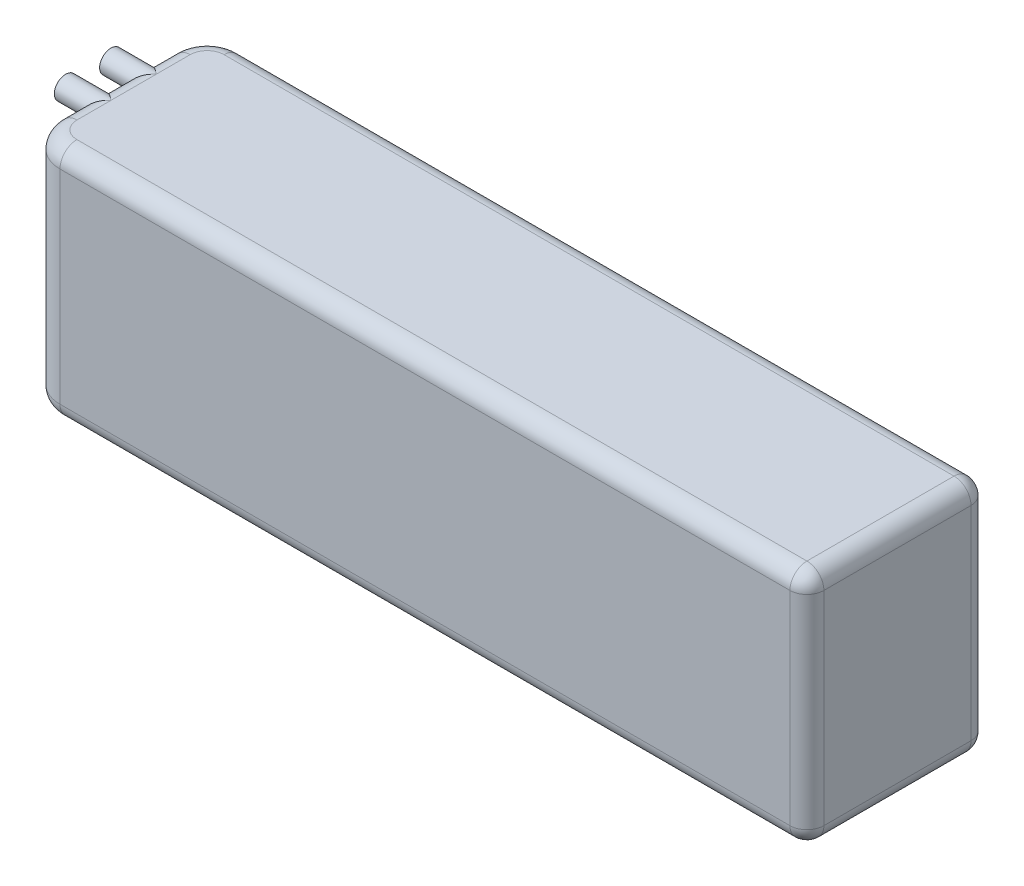
SolidWorks part; units mm, degrees
ref_plane "Front Plane" through (0, 0, 0) normal (0, 0, 1) x (1, 0, 0)
ref_plane "Top Plane" through (0, 0, 0) normal (0, 1, 0) x (1, 0, 0)
ref_plane "Right Plane" through (0, 0, 0) normal (1, 0, 0) x (0, 0, -1)
sketch "Sketch1" plane through (0, 0, 0) normal (0, 1, 0) x (1, 0, 0)
  line L1 (0, 0) -> (138, 0)
  line L2 (0, 0) -> (0, 32)
  line L3 (0, 32) -> (138, 32)
  line L4 (138, 0) -> (138, 32)
  dimension "D1" = 138
  dimension "D2" = 32
extrude "Boss-Extrude1" add sketch "Sketch1" along normal blind 42
sketch "Sketch2" plane through (0, 0, 0) normal (-1, 0, 0) x (0, 0, 1)
  line L0 (-32, 42) -> (0, 42) construction
  line L1 (-16, 42) -> (-16, 0) construction
  line L2 (-32, 0) -> (0, 0) construction
  circle A0 centre (-12, 40) radius 2
  circle A1 centre (-20, 40) radius 2
  dimension "D1" = 4
  dimension "D2" = 4
  dimension "D3" = 8
  dimension "D4" = 2
  dimension "D5" = 4
extrude "Boss-Extrude2" add sketch "Sketch2" along normal blind 5
fillet "Fillet1" radius 6 2 edges at (0, 21, -32) (0, 21, 0)
fillet "Fillet2" radius 3 16 edges at (1.7574, 42, -1.7574) (0, 42, -9) (0, 42, -23) (0, 42, -16) (1.7574, 42, -30.2426) (72, 42, -32) (138, 42, -16) (138, 21, -32) (138, 21, 0) (72, 42, 0) (1.7574, 0, -1.7574) (72, 0, 0) (138, 0, -16) (72, 0, -32) (1.7574, 0, -30.2426) (0, 0, -16)
